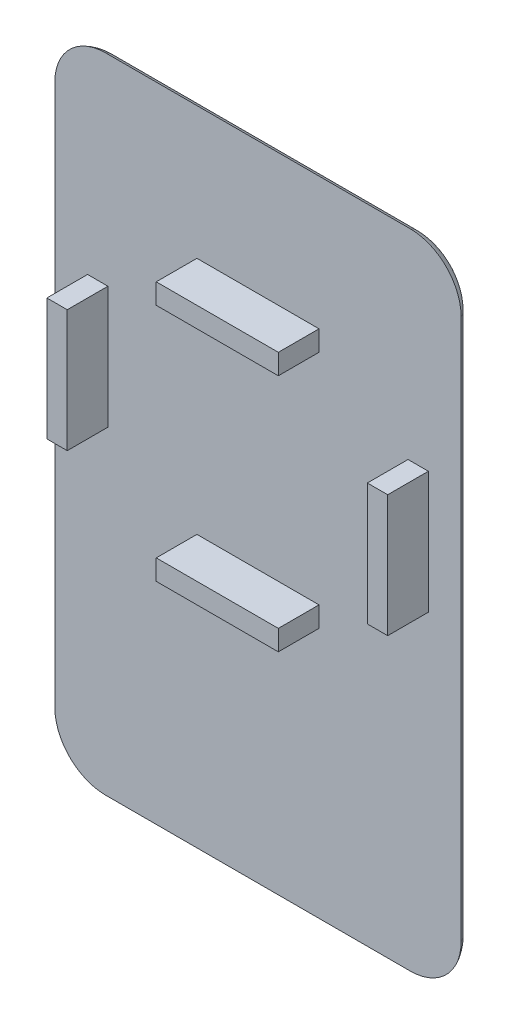
SolidWorks part; units mm, degrees
ref_plane "前视基准面" through (0, 0, 0) normal (0, 0, 1) x (1, 0, 0)
ref_plane "上视基准面" through (0, 0, 0) normal (0, 1, 0) x (1, 0, 0)
ref_plane "右视基准面" through (0, 0, 0) normal (1, 0, 0) x (0, 0, -1)
sketch "草图1" plane through (0, 0, 0) normal (0, 0, 1) x (1, 0, 0)
  line L1 (-19.97, 31.595) -> (19.97, 31.595)
  line L2 (-19.97, 31.595) -> (-19.97, -31.595)
  line L3 (-19.97, -31.595) -> (19.97, -31.595)
  line L4 (19.97, 31.595) -> (19.97, -31.595)
  line L5 (-19.97, 31.595) -> (19.97, -31.595) construction
  line L6 (-19.97, -31.595) -> (19.97, 31.595) construction
  point P0 (0, 0)
  dimension "D1" = 39.94
  dimension "D2" = 63.19
extrude "凸台-拉伸1" add sketch "草图1" along normal blind 1.2
fillet "圆角1" radius 5 4 edges at (-19.97, 31.595, 0.6) (19.97, 31.595, 0.6) (19.97, -31.595, 0.6) (-19.97, -31.595, 0.6)
fillet "圆角3" radius 2 8 edges at (-18.5055, -30.1305, 0) (0, -31.595, 0) (18.5055, -30.1305, 0) (19.97, 0, 0) (18.5055, 30.1305, 0) (0, 31.595, 0) (-18.5055, 30.1305, 0) (-19.97, 0, 0)
sketch "草图5" plane through (0, 0, 1.2) normal (0, 0, 1) x (1, 0, 0)
  line L0 (0, 31.595) -> (0, -31.595) construction
  line L1 (14.97, 31.595) -> (-14.97, 31.595) construction
  line L2 (-14.97, -31.595) -> (14.97, -31.595) construction
  line L3 (-14.75, -0.155) -> (-16.75, -0.155)
  line L4 (-6, 18.595) -> (6, 18.595)
  line L5 (-6, 18.595) -> (-6, 16.595)
  line L6 (-6, 16.595) -> (6, 16.595)
  line L7 (6, 18.595) -> (6, 16.595)
  line L8 (-6, 18.595) -> (6, 16.595) construction
  line L9 (-6, 16.595) -> (6, 18.595) construction
  line L10 (-6, -4.905) -> (6, -4.905)
  line L11 (-6, -4.905) -> (-6, -6.905)
  line L12 (-6, -6.905) -> (6, -6.905)
  line L13 (6, -4.905) -> (6, -6.905)
  line L14 (-6, -4.905) -> (6, -6.905) construction
  line L15 (-6, -6.905) -> (6, -4.905) construction
  line L16 (14.75, 11.845) -> (16.75, 11.845)
  line L17 (14.75, 11.845) -> (14.75, -0.155)
  line L18 (14.75, -0.155) -> (16.75, -0.155)
  line L19 (16.75, 11.845) -> (16.75, -0.155)
  line L20 (14.75, 11.845) -> (16.75, -0.155) construction
  line L21 (14.75, -0.155) -> (16.75, 11.845) construction
  line L22 (-14.75, 11.845) -> (-14.75, -0.155)
  line L23 (-16.75, 11.845) -> (-16.75, -0.155)
  line L24 (-14.75, 11.845) -> (-16.75, 11.845)
  point P6 (0, 17.595)
  point P11 (0, -5.905)
  point P16 (15.75, 5.845)
  dimension "D1" = 12
  dimension "D2" = 2
  dimension "D3" = 12
  dimension "D4" = 2
  dimension "D5" = 21.5
  dimension "D6" = 12
  dimension "D7" = 2
  dimension "D8" = 4.75
  dimension "D9" = 29.5
  dimension "D10" = 13
extrude "凸台-拉伸4" add sketch "草图5" along normal blind 4
